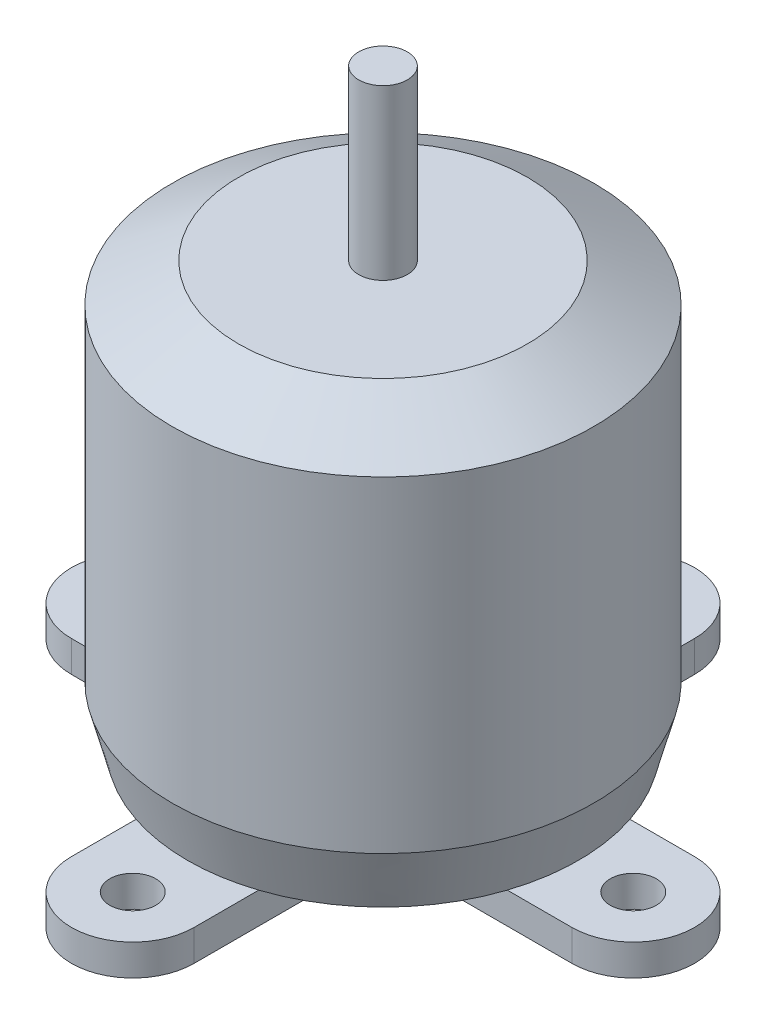
SolidWorks part; units mm, degrees
ref_plane "Front Plane" through (0, 0, 0) normal (0, 0, 1) x (1, 0, 0)
ref_plane "Top Plane" through (0, 0, 0) normal (0, 1, 0) x (1, 0, 0)
ref_plane "Right Plane" through (0, 0, 0) normal (1, 0, 0) x (0, 0, -1)
sketch "Sketch1" plane through (0, 0, 0) normal (0, 1, 0) x (1, 0, 0)
  circle A0 centre (0, 0) radius 13.75
  dimension "D1" = 27.5
extrude "Boss-Extrude1" add sketch "Sketch1" along normal blind 27.5
sketch "Sketch3" plane through (0, 27.5, 0) normal (0, 1, 0) x (1, 0, 0)
  circle A0 centre (0, 0) radius 1.585
  dimension "D1" = 3.17
extrude "Boss-Extrude2" add sketch "Sketch3" along normal blind 11
chamfer "Chamfer1" distance 2.5 angle 60 1 edges at (0, 27.5, 13.75) first distance on face at (0, 27.5, 13.75)
chamfer "Chamfer2" distance 1 angle 75 1 edges at (0, 0, 13.75) first distance on face at (0, 0, 13.75)
sketch "Sketch4" plane through (0, 0, 0) normal (0, -1, 0) x (1, 0, 0)
  line L0 (0, 12.32) -> (0, 20.32) construction
  line L1 (0, -54.6947) -> (0, 54.6947) construction
  line L2 (4, 16.32) -> (4, 9)
  line L3 (-4, 16.32) -> (-4, 9)
  line L4 (-4, 4) -> (0, 0) construction
  line L5 (0, 0) -> (4, 4) construction
  line L6 (15.125, 0) -> (-15.125, 0) construction
  line L7 (16.32, -4) -> (9, -4)
  line L8 (16.32, 4) -> (9, 4)
  line L9 (-4, -16.32) -> (-4, -9)
  line L10 (4, -16.32) -> (4, -9)
  line L11 (-16.32, 4) -> (-9, 4)
  line L12 (-16.32, -4) -> (-9, -4)
  arc A0 (4, 16.32) -> (-4, 16.32) centre (0, 16.32) ccw
  circle A1 centre (0, 16.32) radius 1.5
  arc A2 (16.32, -4) -> (16.32, 4) centre (16.32, 0) ccw
  circle A3 centre (16.32, 0) radius 1.5
  arc A4 (-4, -16.32) -> (4, -16.32) centre (0, -16.32) ccw
  circle A5 centre (0, -16.32) radius 1.5
  arc A6 (-16.32, 4) -> (-16.32, -4) centre (-16.32, 0) ccw
  circle A7 centre (-16.32, 0) radius 1.5
  arc A8 (9, 4) -> (4, 9) centre (9, 9) cw
  arc A9 (-9, 4) -> (-4, 9) centre (-9, 9) ccw
  arc A10 (-4, -9) -> (-9, -4) centre (-9, -9) ccw
  arc A11 (9, -4) -> (4, -9) centre (9, -9) ccw
  point P5 (0, 16.32)
  point P36 (0, 0)
  dimension "D3" = 3
  dimension "D6" = 5
  dimension "D7" = 5
  dimension "D8" = 5
  dimension "D9" = 5
  dimension "D1" = 20.32
  dimension "D2" = 4
  dimension "D4" = 45
  dimension "D10" = 23.08
  dimension "D5" = 4
extrude "Boss-Extrude3" add sketch "Sketch4" along normal blind 2.032
